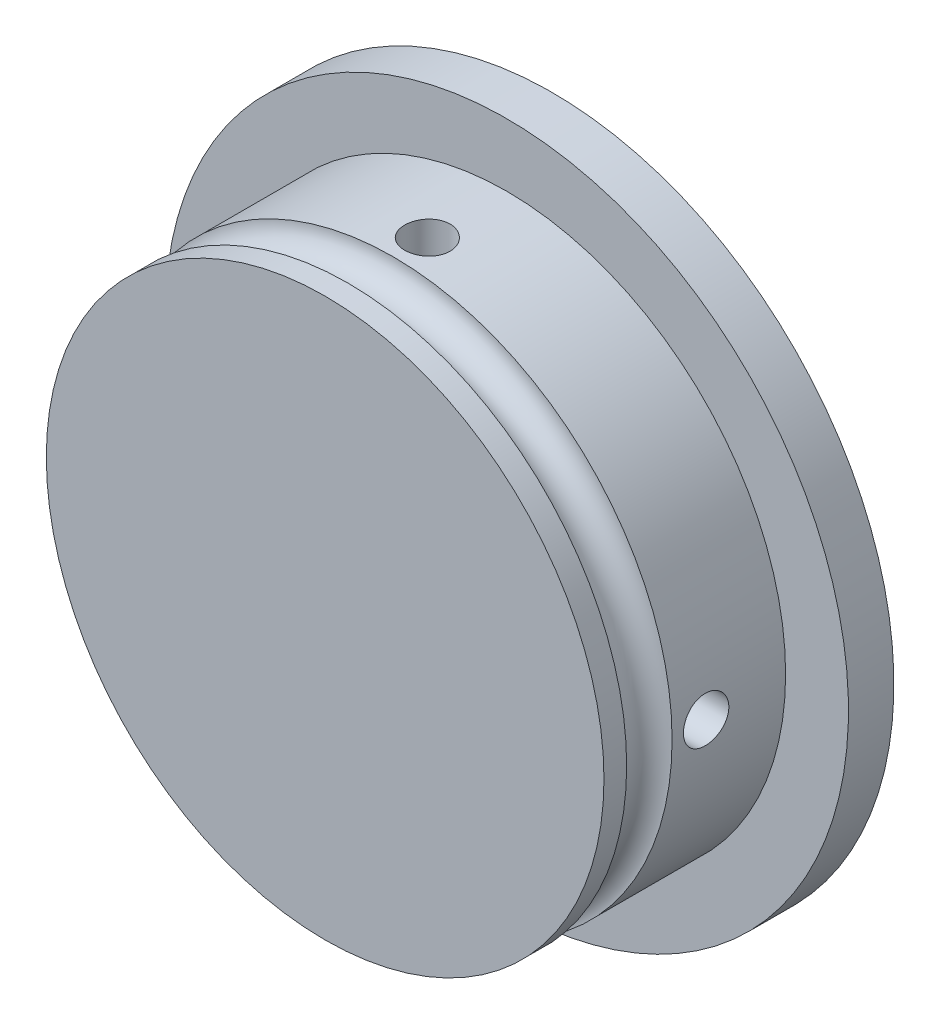
SolidWorks part; units mm, degrees
material "Stainless Steel (ferritic)"
ref_plane "Front Plane" through (0, 0, 0) normal (0, 0, 1) x (1, 0, 0)
ref_plane "Top Plane" through (0, 0, 0) normal (0, 1, 0) x (1, 0, 0)
ref_plane "Right Plane" through (0, 0, 0) normal (1, 0, 0) x (0, 0, -1)
sketch "Sketch1" plane through (0, 0, 0) normal (0, 1, 0) x (1, 0, 0)
  line L0 (0, 0) -> (0, 20)
  line L1 (0, 20) -> (45, 20)
  line L2 (45, 20) -> (45, 16)
  line L3 (45, 16) -> (24.5618, 16)
  line L4 (24.5618, 16) -> (24.5618, 6)
  line L9 (0, 0) -> (24.5618, 0)
  line L10 (0, 0) -> (0, -10) construction
  line L11 (30.099, 16) -> (30.099, 20)
  line L12 (24.5618, 0) -> (24.5618, 2)
  arc A0 (24.5618, 6) -> (24.5618, 2) centre (24.5618, 4) ccw
  point P9 (0, 0)
  dimension "D1" = 24.5618
  dimension "D7" = 2
  dimension "D2" = 4
  dimension "D3" = 10
  dimension "D4" = 20
  dimension "D6" = 45
  dimension "D8" = 10
  dimension "D9" = 30.099
revolve "Revolve1" add sketch "Sketch1" angle 360 about L10 region at (12.7966, 0, -10.4238)
sketch "Sketch2" plane through (0, 0, -16) normal (0, 0, 1) x (1, 0, 0)
  circle A0 centre (0, 0) radius 37.5 construction
  point P0 (0, 37.5)
  point P2 (37.5, 0)
  point P4 (0, -37.5)
  point P6 (-37.5, 0)
  dimension "D1" = 75
ref_plane "Plane1" through (0, 0, -6) normal (0, 0, 1) x (1, 0, 0)
ref_plane "Plane2" through (0, 0, -9) normal (0, 0, 1) x (1, 0, 0)
hole_wizard "Ø4.0mm Dowel Hole2" positions "3DSketch1" profile "Sketch5" hole size "Ø4.0" standard "ISO"
sketch3d "3DSketch1"
  line L0 (24.5618, 0, -9) -> (-24.5618, 0, -9)
  line L2 (0, -24.5618, -9) -> (0, 24.5618, -9)
  point P0 (0, 24.5618, -9)
  point P2 (24.5618, 0, -9)
  point P4 (0, -24.5618, -9)
  point P6 (-24.5618, 0, -9)
  point P15 (-24.5618, 0, -9)
  point P17 (0, 24.5618, -9)
  point P19 (24.5618, 0, -9)
  point P21 (0, -24.5618, -9)
  point P24 (0, -24.5618, -11)
  point P25 (-24.5618, 0, -11)
  point P26 (0, 24.5618, -11)
  point P27 (24.5618, 0, -11)
  point P28 (0, 0, 0)
  point P29 (0, 0, 0)
  point P30 (0, 0, 0)
  point P31 (0, 0, 0)
  point P32 (0, 0, 0)
  dimension "D1" = 0
sketch "Sketch5" plane through (0, -24.5618, -9) normal (1, 0, 0) x (0, 0, -1)
  line L0 (0, 0) -> (0, 9.2017)
  line L1 (0, 9.2017) -> (2, 8)
  line L2 (2, 8) -> (2, 0)
  line L5 (2, 0) -> (0, 0)
  line L10 (0, 9.2017) -> (-2, 8) construction
  line L11 (0, -6.35) -> (0, 107.95) construction
  dimension "Hole Dia." = 4
  dimension "Hole Depth" = 8
  dimension "Drill Angle" = 118
hole_wizard "Ø6.0mm Dowel Hole1" positions "Sketch6" profile "Sketch7" hole size "Ø6.0" standard "ISO"
sketch "Sketch6" plane through (0, 0, -20) normal (0, 0, -1) x (-1, 0, 0)
  point P0 (0, 0)
sketch "Sketch7" plane through (0, 0, -20) normal (1, 0, 0) x (0, 1, 0)
  line L0 (0, 0) -> (0, 16.8026)
  line L1 (0, 16.8026) -> (3, 15)
  line L2 (3, 15) -> (3, 0)
  line L5 (3, 0) -> (0, 0)
  line L10 (0, 16.8026) -> (-3, 15) construction
  line L11 (0, -6.35) -> (0, 107.95) construction
  dimension "Hole Dia." = 6
  dimension "Hole Depth" = 15
  dimension "Drill Angle" = 118
